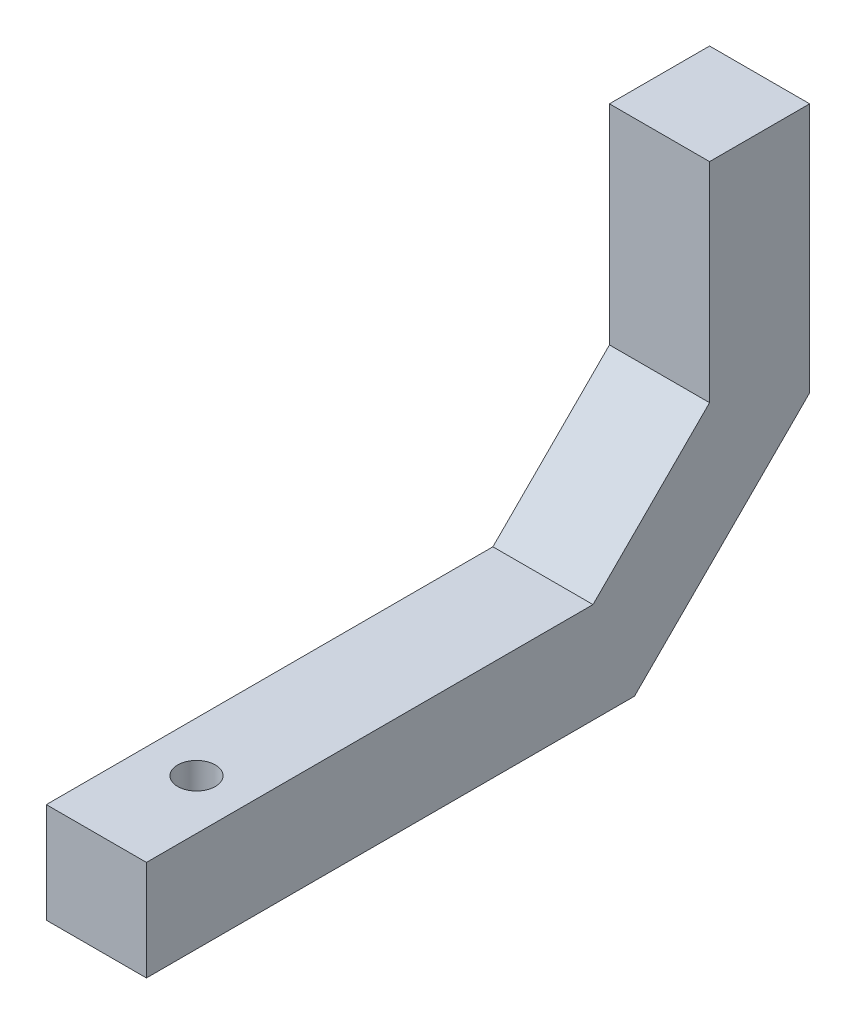
SolidWorks part; units mm, degrees
ref_plane "Front Plane" through (0, 0, 0) normal (0, 0, 1) x (1, 0, 0)
ref_plane "Top Plane" through (0, 0, 0) normal (0, 1, 0) x (1, 0, 0)
ref_plane "Right Plane" through (0, 0, 0) normal (1, 0, 0) x (0, 0, -1)
ref_axis "Z" through (0, 0, 55.65) along (0, 0, -1)
sketch "Sketch1" plane through (0, 0, 0) normal (1, 0, 0) x (0, 0, -1)
  line L0 (-8, 4) -> (0, 4)
  line L1 (0, 4) -> (0, -16)
  line L2 (0, -16) -> (-14, -30)
  line L3 (-14, -30) -> (-45, -30)
  line L4 (-45, -30) -> (-45, -22) construction
  line L5 (-45, -22) -> (-17.3137, -22)
  line L6 (-17.3137, -22) -> (-8, -12.6863)
  line L7 (-8, -12.6863) -> (-8, 4)
  line L8 (-13.4134, -18.0997) -> (-7.7566, -23.7566) construction
  line L10 (-45, -22) -> (-53, -22)
  line L11 (-45, -22) -> (-45, -30) construction
  line L12 (-45, -30) -> (-53, -30)
  line L13 (-53, -22) -> (-53, -30)
  dimension "D1" = 8
  dimension "D2" = 45
  dimension "D3" = 30
  dimension "D4" = 4
  dimension "D5" = 135
  dimension "D6" = 14
  dimension "D7" = 8
extrude "Boss-Extrude1" add sketch "Sketch1" along normal blind 4 and the other way blind 4
sketch "Sketch3" plane through (0, -22, 0) normal (0, 1, 0) x (1, 0, 0)
  line L0 (-4.4, 0) -> (4.4, 0) construction
  line L1 (0, -18.7) -> (0, 18.7) construction
  circle A0 centre (0, -45) radius 1.5
  dimension "D2" = 3
  dimension "D1" = 45
extrude "Cut-Extrude1" cut sketch "Sketch3" against normal through all
ref_axis "Axis1" through (0, -22, 45) along (0, 1, 0)
equation "\"rbracket-width\"= 8"
equation "\"D1@Boss-Extrude1\"=\"rbracket-width\"/2"
equation "\"D2@Boss-Extrude1\"=\"rbracket-width\"/2"
equation "\"EyeCaptureRadius\"= ( \"EyeDiameter\" + \"EyeClearance\" ) / 2"
equation "\"rbracket_planetocenterline_dist\"= \"BasePlaneDistance\""
equation "\"D2@Sketch1\"=\"rbracket_planetocenterline_dist\""
equation "\"EyeDiameter\" = 28"
equation "\"BasePlaneDistance\" = 45"
equation "\"EyeClearance\" = 2"
equation "\"D1@Sketch1\"=\"rbracket-width\""
equation "\"D3@Sketch1\"=(\"EyeDiameter\"+\"EyeClearance\"+\"EyeClearance\")/2 + \"L2Thickness\" + \"rbracket-width\""
equation "\"D4@Sketch1\"=\"rbracket-width\"/2"
equation "\"D6@Sketch1\"=\"EyeDiameter\"/2"
equation "\"D7@Sketch1\"=\"rbracket-width\""
equation "\"D1@Sketch3\"=\"BasePlaneDistance\""
equation "\"L2Thickness\" = 6"
